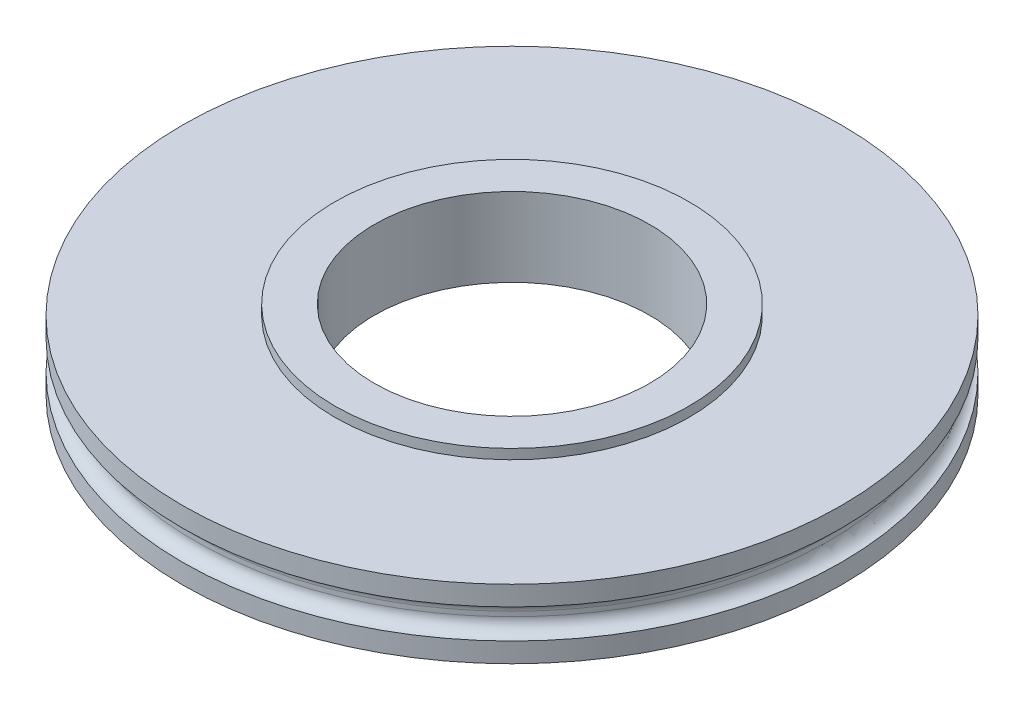
SolidWorks part; units mm, degrees
ref_plane "Front Plane" through (0, 0, 0) normal (0, 0, 1) x (1, 0, 0)
ref_plane "Top Plane" through (0, 0, 0) normal (0, 1, 0) x (1, 0, 0)
ref_plane "Right Plane" through (0, 0, 0) normal (1, 0, 0) x (0, 0, -1)
sketch "Sketch1" plane through (0, 0, 0) normal (0, 1, 0) x (1, 0, 0)
  circle A0 centre (0, 0) radius 26.5906
  dimension "D1" = 53.1812
extrude "Boss-Extrude1" add sketch "Sketch1" along normal blind 1.5875
sketch "Sketch2" plane through (0, 1.5875, 0) normal (0, 1, 0) x (1, 0, 0)
  circle A0 centre (0, 0) radius 25.5984
  dimension "D1" = 51.1969
extrude "Boss-Extrude2" add sketch "Sketch2" along normal blind 2.3813
sketch "Sketch3" plane through (0, 3.9688, 0) normal (0, 1, 0) x (1, 0, 0)
  circle A0 centre (0, 0) radius 26.5906
extrude "Boss-Extrude3" add sketch "Sketch3" along normal blind 1.5875
sketch "Sketch5" plane through (0, 5.5563, 0) normal (0, 1, 0) x (1, 0, 0)
  circle A0 centre (0, 0) radius 14.2875
extrude "Boss-Extrude4" add sketch "Sketch5" along normal blind 0.7937
sketch "Sketch6" plane through (0, 6.35, 0) normal (0, 1, 0) x (1, 0, 0)
  circle A0 centre (0, 0) radius 11.1125
extrude "Cut-Extrude1" cut sketch "Sketch6" against normal through all
fillet "Fillet1" radius 1 1 edges at (0, 1.5875, 25.5984)
fillet "Fillet2" radius 1 1 edges at (0, 3.9688, 25.5984)
